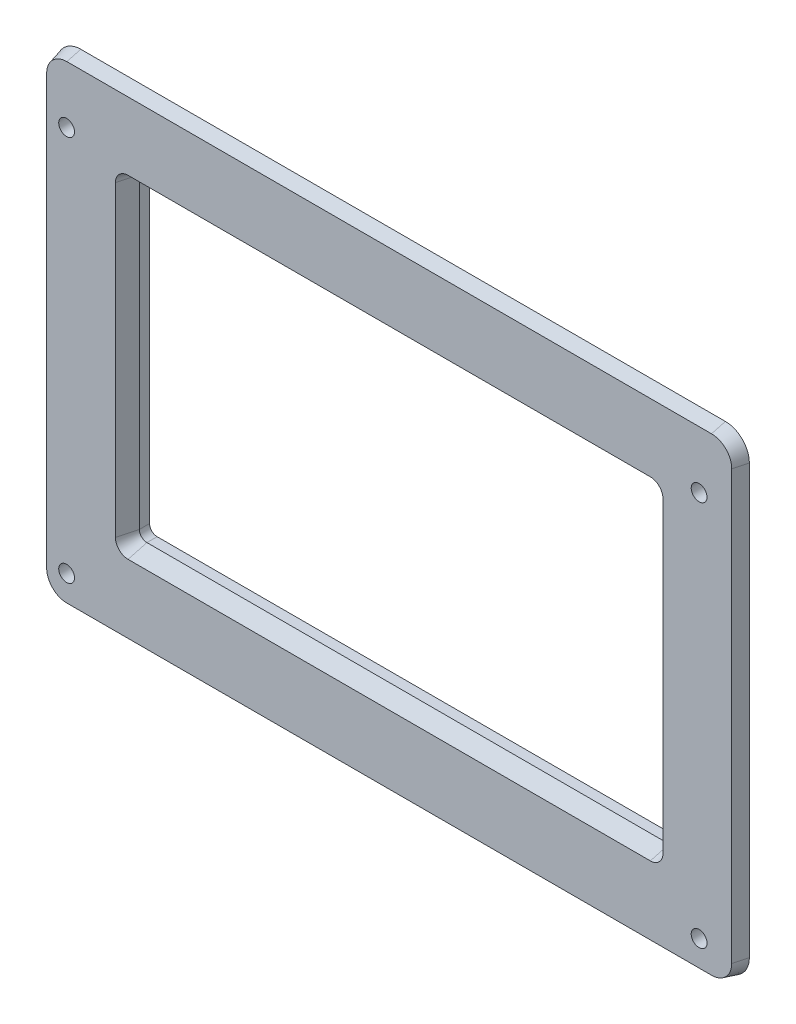
SolidWorks part; units mm, degrees
ref_plane "Front Plane" through (0, 0, 0) normal (0, 0, 1) x (1, 0, 0)
ref_plane "Top Plane" through (0, 0, 0) normal (0, 1, 0) x (1, 0, 0)
ref_plane "Right Plane" through (0, 0, 0) normal (1, 0, 0) x (0, 0, -1)
sketch "Sketch1" plane through (0, 0, 0) normal (0, 0, 1) x (1, 0, 0)
  line L1 (-69.85, -48.133) -> (69.85, -48.133)
  line L2 (-69.85, -48.133) -> (-69.85, 48.133)
  line L3 (-69.85, 48.133) -> (69.85, 48.133)
  line L4 (69.85, -48.133) -> (69.85, 48.133)
  line L5 (-69.85, -48.133) -> (69.85, 48.133) construction
  line L6 (-69.85, 48.133) -> (69.85, -48.133) construction
  point P0 (0, 0)
  dimension "D1" = 139.7
  dimension "D2" = 96.266
extrude "Boss-Extrude1" add sketch "Sketch1" along normal blind 2.794
hole_wizard "1/8 (0.125) Diameter Hole1" positions "Sketch2" profile "Sketch3" hole size "1/8" standard "ANSI Inch" end condition through all
sketch "Sketch2" plane through (0, 0, 2.794) normal (0, 0, 1) x (1, 0, 0)
  line L0 (-1.27, 0) -> (-1.27, 41.7504) construction
  line L4 (-1.27, -3.175) -> (86.3038, -3.175) construction
  line L5 (69.85, 48.133) -> (-69.85, 48.133) construction
  line L6 (69.85, -48.133) -> (69.85, 48.133) construction
  point P0 (-64.82, -41.975)
  point P11 (-64.82, 35.625)
  point P13 (62.28, -41.975)
  point P14 (62.28, 35.625)
  dimension "D1" = 127.1
  dimension "D2" = 77.6
  dimension "D3" = 51.308
  dimension "D4" = 71.12
sketch "Sketch3" plane through (-64.82, -41.975, 2.794) normal (1, 0, 0) x (0, -1, 0)
  line L0 (0, 0) -> (0, 2.794)
  line L1 (0, 2.794) -> (1.5875, 2.794)
  line L2 (1.5875, 2.794) -> (1.5875, 0)
  line L5 (1.5875, 0) -> (0, 0)
  line L11 (0, -6.35) -> (0, 107.95) construction
  dimension "Thru Hole Dia." = 3.175
  dimension "Thru Hole Depth" = 2.794
sketch "Sketch4" plane through (0, 0, 2.794) normal (0, 0, 1) x (1, 0, 0)
  line L0 (-69.85, 48.133) -> (-69.85, -48.133) construction
  line L1 (-54, -32.3388) -> (54, -32.3388)
  line L2 (-54, -32.3388) -> (-54, 32.4612)
  line L3 (-54, 32.4612) -> (54, 32.4612)
  line L4 (54, -32.3388) -> (54, 32.4612)
  line L5 (-54, -32.3388) -> (54, 32.4612) construction
  line L6 (-54, 32.4612) -> (54, -32.3388) construction
  line L8 (69.85, 48.133) -> (-69.85, 48.133) construction
  line L9 (69.85, -48.133) -> (69.85, 48.133) construction
  line L10 (-69.85, -48.133) -> (69.85, -48.133) construction
  point P0 (0, 0.0612)
  dimension "D1" = 108
  dimension "D2" = 64.8
  dimension "D3" = 48.0718
  dimension "D4" = 69.85
  dimension "D5" = 15.85
  dimension "D6" = 15.85
  dimension "D7" = 15.6718
  dimension "D8" = 15.7942
extrude "Cut-Extrude1" cut sketch "Sketch4" against normal through all
fillet "Fillet1" radius 1.524 4 edges at (-54, -32.3388, 1.397) (54, -32.3388, 1.397) (54, 32.4612, 1.397) (-54, 32.4612, 1.397)
fillet "Fillet2" radius 5.08 4 edges at (-69.85, -48.133, 1.397) (69.85, -48.133, 1.397) (69.85, 48.133, 1.397) (-69.85, 48.133, 1.397)
sketch "Sketch5" plane through (0, 0, 0) normal (0, 0, -1) x (-1, 0, 0)
  line L0 (-54, -30.8148) -> (-54, 30.9372) construction
  line L1 (-56.54, -34.8788) -> (56.54, -34.8788)
  line L2 (-56.54, -34.8788) -> (-56.54, 34.8788)
  line L3 (-56.54, 34.8788) -> (56.54, 34.8788)
  line L4 (56.54, -34.8788) -> (56.54, 34.8788)
  line L5 (-56.54, -34.8788) -> (56.54, 34.8788) construction
  line L6 (-56.54, 34.8788) -> (56.54, -34.8788) construction
  line L7 (52.476, -32.3388) -> (-52.476, -32.3388) construction
  line L8 (-54, -30.8148) -> (-54, 30.9372)
  line L9 (54, 30.9372) -> (54, -30.8148) construction
  line L10 (54, 30.9372) -> (54, -30.8148)
  line L11 (52.476, -32.3388) -> (-52.476, -32.3388)
  line L12 (-52.476, 32.4612) -> (52.476, 32.4612) construction
  line L13 (-52.476, 32.4612) -> (52.476, 32.4612)
  arc A0 (52.476, -32.3388) -> (54, -30.8148) centre (52.476, -30.8148) ccw construction
  arc A1 (-54, -30.8148) -> (-52.476, -32.3388) centre (-52.476, -30.8148) ccw construction
  arc A2 (52.476, -32.3388) -> (54, -30.8148) centre (52.476, -30.8148) ccw
  arc A3 (-54, -30.8148) -> (-52.476, -32.3388) centre (-52.476, -30.8148) ccw
  arc A4 (-52.476, 32.4612) -> (-54, 30.9372) centre (-52.476, 30.9372) ccw construction
  arc A5 (54, 30.9372) -> (52.476, 32.4612) centre (52.476, 30.9372) ccw construction
  arc A6 (-52.476, 32.4612) -> (-54, 30.9372) centre (-52.476, 30.9372) ccw
  arc A7 (54, 30.9372) -> (52.476, 32.4612) centre (52.476, 30.9372) ccw
  point P0 (0, 0)
  dimension "D1" = 2.54
  dimension "D2" = 2.54
extrude "Boss-Extrude2" add sketch "Sketch5" along normal blind 3.048
fillet "Fillet3" radius 1.524 4 edges at (56.54, 34.8788, -1.524) (56.54, -34.8788, -1.524) (-56.54, 34.8788, -1.524) (-56.54, -34.8788, -1.524)
chamfer "Chamfer1" distance 1.016 angle 75 8 edges at (0, -32.3388, 2.794) (53.5536, -31.8924, 2.794) (-53.5536, -31.8924, 2.794) (54, 0.0612, 2.794) (-54, 0.0612, 2.794) (53.5536, 32.0148, 2.794) (-53.5536, 32.0148, 2.794) (0, 32.4612, 2.794) first distance on face at (0, 0.0612, 2.794)
chamfer "Chamfer2" distance 1.016 angle 75 8 edges at (-69.85, 0, 2.794) (-68.3621, -46.6451, 2.794) (0, -48.133, 2.794) (68.3621, -46.6451, 2.794) (69.85, 0, 2.794) (68.3621, 46.6451, 2.794) (0, 48.133, 2.794) (-68.3621, 46.6451, 2.794) first distance on face at (0, 0.0612, 2.794)
